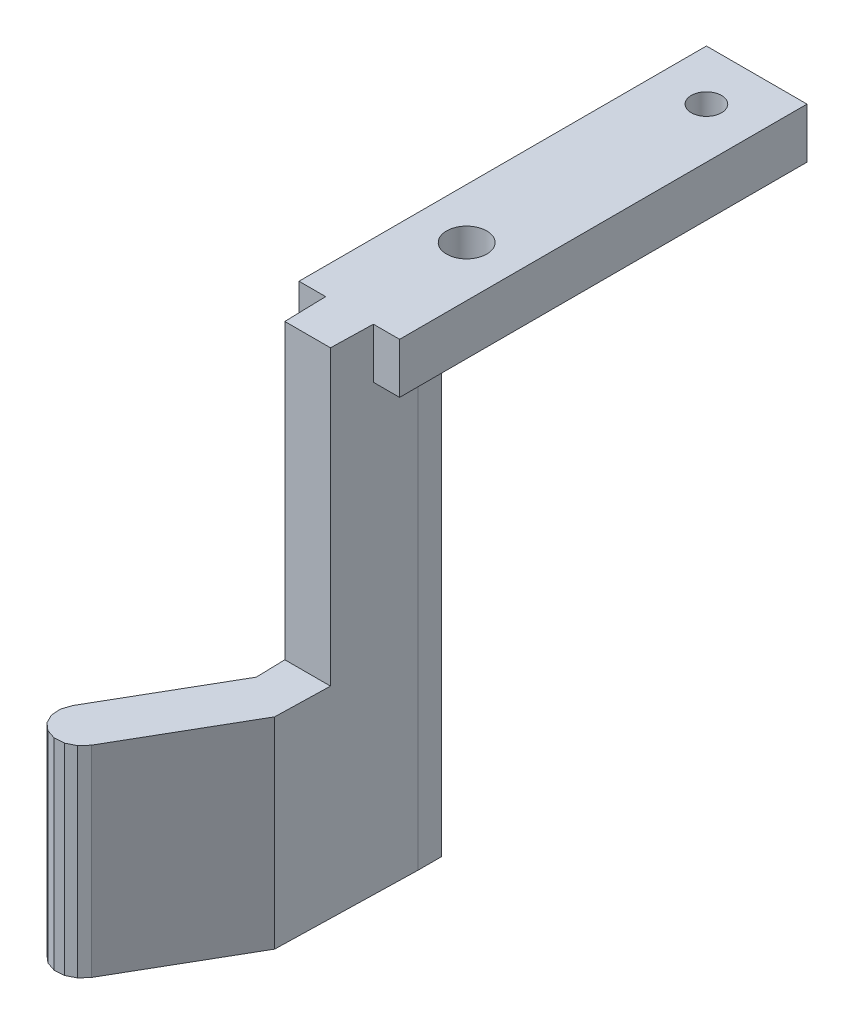
SolidWorks part; units mm, degrees
ref_plane "Front Plane" through (0, 0, 0) normal (0, 0, 1) x (1, 0, 0)
ref_plane "Top Plane" through (0, 0, 0) normal (0, 1, 0) x (1, 0, 0)
ref_plane "Right Plane" through (0, 0, 0) normal (1, 0, 0) x (0, 0, -1)
sketch "Sketch1" plane through (0, 0, 0) normal (0, 0, 1) x (1, 0, 0)
  line L0 (14.8, 20.475) -> (20.8, 20.475)
  line L1 (20.8, 20.475) -> (20.8, 23.475)
  line L2 (20.8, 23.475) -> (14.8, 23.475)
  line L3 (14.8, 23.475) -> (14.8, 20.475)
extrude "Boss-Extrude1" add sketch "Sketch1" along normal blind 24.3 from offset 7.2
sketch "Sketch2" plane through (0, 0, 0) normal (0, 1, 0) x (1, 0, 0)
  line L0 (16.3, -27.5) -> (16.3, -28.0981)
  line L1 (16.3, -28.0981) -> (16.501, -35.75)
  line L2 (16.501, -35.75) -> (12.501, -42.6782)
  line L3 (12.501, -42.6782) -> (12.3128, -43.2324)
  line L4 (12.3128, -43.2324) -> (12.3511, -43.8164)
  line L5 (12.3511, -43.8164) -> (12.61, -44.3413)
  line L6 (12.61, -44.3413) -> (13.05, -44.7272)
  line L7 (13.05, -44.7272) -> (13.6042, -44.9154)
  line L8 (13.6042, -44.9154) -> (14.1882, -44.8771)
  line L9 (14.1882, -44.8771) -> (14.7131, -44.6182)
  line L10 (14.7131, -44.6182) -> (15.099, -44.1782)
  line L11 (15.099, -44.1782) -> (19.099, -37.25)
  line L12 (19.099, -37.25) -> (19.3, -28.9019)
  line L13 (19.3, -28.9019) -> (19.3, -27.5)
  line L14 (19.3, -27.5) -> (16.3, -27.5)
extrude "Boss-Extrude2" add sketch "Sketch2" along normal blind 29.475 from offset 6 offset against normal yes
sketch "Sketch3" plane through (0, 0, 0) normal (0, 1, 0) x (1, 0, 0)
  circle A0 centre (17.8, -24.5) radius 1.2
  circle A1 centre (17.8, -10.2) radius 0.9
extrude "Cut-Extrude1" cut sketch "Sketch3" against normal through all and the other way through all
sketch "Sketch4" plane through (0, 0, 0) normal (1, 0, 0) x (0, 0, -1)
  line L0 (-34, 6) -> (-34, 24.475)
  line L1 (-34, 24.475) -> (-80, 24.475)
  line L2 (-80, 24.475) -> (-80, 6)
  line L3 (-80, 6) -> (-34, 6)
extrude "Cut-Extrude2" cut sketch "Sketch4" against normal through all and the other way through all
